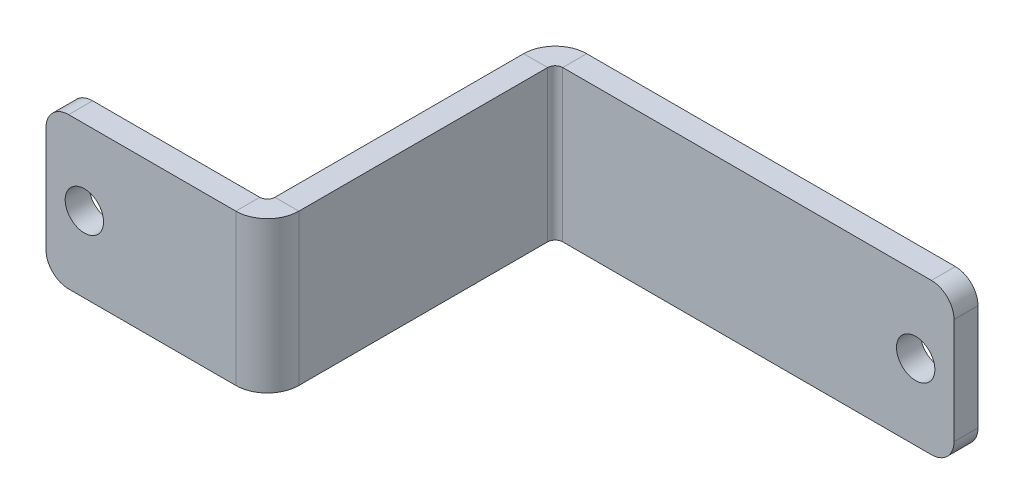
SolidWorks part; units mm, degrees
note: The reader was unsure of these and kept them because the rebuilt part matched: flange length of "Edge-Flange1", "Edge-Flange2".
material "Custom Plastic"
ref_plane "X-Y Datum" through (0, 0, 0) normal (0, 0, 1) x (1, 0, 0)
ref_plane "X-Z Datum" through (0, 0, 0) normal (0, 1, 0) x (1, 0, 0)
ref_plane "Y-Z Datum" through (0, 0, 0) normal (1, 0, 0) x (0, 0, -1)
sketch "Sketch1" plane through (0, 0, -1949.6834) normal (0, 0, 1) x (1, 0, 0)
  line L7 (74.8293, 321.1281) -> (100.9696, 321.1281)
  line L8 (74.8293, 321.1281) -> (74.8293, 301.1281)
  line L9 (74.8293, 301.1281) -> (100.9696, 301.1281)
  line L10 (100.9696, 321.1281) -> (100.9696, 301.1281)
  point P4 (0, 0)
  point P5 (0, 0)
  point P10 (74.8293, 311.1281)
base flange "Base-Flange1" sketch "Sketch1" thickness 3.175 reverse thickness direction yes parameters "D1"=10
edge flange "Edge-Flange1" sketch "Sketch13" flange angle 90 flange length 38.1204 flange position material outside bend radius 1 thickness 3.175 relief rectangular parameters "D6"=10
bend "EdgeBend3" bend radius 1 bend angle 90 parameters "D5"=1
sketch "Sketch13" plane through (100.9696, 0, -1949.6834) normal (-1, 0, 0) x (0, 1, 0)
  line L0 (321.1281, 0) -> (301.1281, 0) construction
  line L1 (321.1281, 0) -> (301.1281, 0)
  line L2 (321.1281, 0) -> (321.1281, 34.9454)
  line L3 (321.1281, 34.9454) -> (301.1281, 34.9454)
  line L4 (301.1281, 34.9454) -> (301.1281, 0)
edge flange "Edge-Flange2" sketch "Sketch15" flange angle 90 flange length 56 flange position material outside bend radius 1 thickness 3.175 relief rectangular parameters "D6"=10
bend "EdgeBend4" bend radius 1 bend angle 90 parameters "D5"=2
sketch "Sketch15" plane through (104.1446, 0, -1984.6288) normal (0, 0, 1) x (0, -1, 0)
  line L0 (-301.1281, 0) -> (-321.1281, 0) construction
  line L1 (-301.1281, 0) -> (-321.1281, 0)
  line L2 (-301.1281, 0) -> (-301.1281, 52.825)
  line L3 (-301.1281, 52.825) -> (-321.1281, 52.825)
  line L4 (-321.1281, 52.825) -> (-321.1281, 0)
fillet "Fillet1" radius 3 4 edges at (74.8293, 301.1281, -1948.0959) (74.8293, 321.1281, -1948.0959) (156.9696, 301.1281, -1986.2163) (156.9696, 321.1281, -1986.2163)
sketch "Sketch18" plane through (0, 0, -1946.5084) normal (0, 0, 1) x (1, 0, 0)
  line L0 (74.8293, 311.1281) -> (79.9093, 311.1281)
  line L1 (74.8293, 318.1281) -> (74.8293, 304.1281) construction
  circle A0 centre (79.9093, 311.1281) radius 2.54
  dimension "D1" = 5.08
extrude "Cut-Extrude2" cut sketch "Sketch18" against normal through all
sketch "Sketch19" plane through (0, 0, -1984.6288) normal (0, 0, 1) x (1, 0, 0)
  line L0 (156.9696, 311.1281) -> (151.8896, 311.1281)
  line L1 (156.9696, 304.1281) -> (156.9696, 318.1281) construction
  circle A0 centre (151.8896, 311.1281) radius 2.54
  dimension "D1" = 5.08
  dimension "D2" = 5.08
extrude "Cut-Extrude3" cut sketch "Sketch19" against normal through all
sketch "Bend-Lines1" [suppressed] plane through (0, 0, 0) normal (0, 1, 0) x (1, 0, 0)
sketch "Bounding-Box1" [suppressed] plane through (0, 0, 0) normal (0, 1, 0) x (1, 0, 0)
sheet metal parameters "Sheet-Metal1" thickness 3.175 parameters "D1"=10
flat pattern "Flat-Pattern1" [suppressed]
sketch "Bend-Lines2" plane through (0, 0, 0) normal (0, 1, 0) x (1, 0, 0)
sketch3d "Bounding-Box2" [suppressed]
  line L0 (-74.8293, 301.1281, 0) -> (-100.9696, 301.1281, 0) construction
  line L1 (-74.8293, 321.1281, 0) -> (-100.9696, 321.1281, 0) construction
  line L2 (-74.8293, 301.1281, 0) -> (-74.8293, 321.1281, 0) construction
  line L3 (-100.9696, 301.1281, 0) -> (-100.9696, 321.1281, 0) construction
sheet metal parameters "Sheet-Metal2" thickness 3.175 parameters "D1"=10
flat pattern "Flat-Pattern1"
sketch "Bend-Lines2" plane through (0, 0, -1947.5) normal (0, 0, -1) x (-1, 0, 0)
  line L2 (-102.0018, 321.1281) -> (-102.0018, 301.1281) construction
  line L3 (-102.0018, 321.1281) -> (-102.0018, 301.1281) construction
sketch3d "Bounding-Box2" [suppressed]
  line L0 (-74.8293, 301.1281, 0) -> (-139.859, 301.1281, 0) construction
  line L1 (-74.8293, 321.1281, 0) -> (-139.859, 321.1281, 0) construction
  line L2 (-74.8293, 301.1281, 0) -> (-74.8293, 321.1281, 0) construction
  line L3 (-139.859, 301.1281, 0) -> (-139.859, 321.1281, 0) construction
bend of the flat pattern "Flatten-<EdgeBend3>1"
sheet metal parameters "Sheet-Metal3" thickness 3.175 parameters "D1"=10
flat pattern "Flat-Pattern1"
sketch "Bend-Lines2" plane through (0, 0, -1947.295) normal (0, 0, -1) x (-1, 0, 0)
  line L4 (-140.8913, 321.1281) -> (-140.8913, 301.1281) construction
  line L5 (-102.0018, 321.1281) -> (-102.0018, 301.1281) construction
  line L6 (-140.8913, 321.1281) -> (-140.8913, 301.1281) construction
  line L7 (-102.0018, 321.1281) -> (-102.0018, 301.1281) construction
sketch3d "Bounding-Box2" [suppressed]
  line L0 (-74.8293, 301.1281, 0) -> (-188.7485, 301.1281, 0) construction
  line L1 (-74.8293, 321.1281, 0) -> (-188.7485, 321.1281, 0) construction
  line L2 (-74.8293, 301.1281, 0) -> (-74.8293, 321.1281, 0) construction
  line L3 (-188.7485, 301.1281, 0) -> (-188.7485, 321.1281, 0) construction
bend of the flat pattern "Flatten-<EdgeBend3>2"
bend of the flat pattern "Flatten-<EdgeBend4>1"
sheet metal parameters "Sheet-Metal5" thickness 3.175 parameters "D1"=10
flat pattern "Flat-Pattern1" [suppressed]
sketch "Bend-Lines2" plane through (0, 0, -1947.295) normal (0, 0, -1) x (-1, 0, 0)
  line L4 (-140.8913, 321.1281) -> (-140.8913, 301.1281) construction
  line L5 (-102.0018, 321.1281) -> (-102.0018, 301.1281) construction
  line L6 (-140.8913, 321.1281) -> (-140.8913, 301.1281) construction
  line L7 (-102.0018, 321.1281) -> (-102.0018, 301.1281) construction
sketch3d "Bounding-Box2" [suppressed]
  line L0 (-74.8293, 301.1281, 0) -> (-188.7485, 301.1281, 0) construction
  line L1 (-74.8293, 321.1281, 0) -> (-188.7485, 321.1281, 0) construction
  line L2 (-74.8293, 301.1281, 0) -> (-74.8293, 321.1281, 0) construction
  line L3 (-188.7485, 301.1281, 0) -> (-188.7485, 321.1281, 0) construction
bend of the flat pattern "Flatten-<EdgeBend3>2"
bend of the flat pattern "Flatten-<EdgeBend4>1"
sketch "Sketch19-1" [suppressed] plane through (37.7789, 0, -1944.12) normal (0, 0, 1) x (1, 0, 0)
  line L0 (150.9696, 311.1281) -> (145.8896, 311.1281)
  circle A0 centre (145.8896, 311.1281) radius 2.54
  dimension "D1" = 5.08
  dimension "D2" = 5.08
sheet metal parameters "Sheet-Metal6" thickness 3.175 parameters "D1"=10
flat pattern "Flat-Pattern1" [suppressed]
sketch "Bend-Lines2" plane through (0, 0, -1949.6834) normal (0, 0, -1) x (-1, 0, 0)
  line L4 (-139.0117, 321.1281) -> (-139.0117, 301.1281) construction
  line L5 (-102.0018, 321.1281) -> (-102.0018, 301.1281) construction
  line L6 (-139.0117, 321.1281) -> (-139.0117, 301.1281) construction
  line L7 (-102.0018, 321.1281) -> (-102.0018, 301.1281) construction
sketch3d "Bounding-Box2" [suppressed]
  line L0 (-74.8293, 301.1281, 0) -> (-192.8689, 301.1281, 0) construction
  line L1 (-74.8293, 321.1281, 0) -> (-192.8689, 321.1281, 0) construction
  line L2 (-74.8293, 301.1281, 0) -> (-74.8293, 321.1281, 0) construction
  line L3 (-192.8689, 301.1281, 0) -> (-192.8689, 321.1281, 0) construction
bend of the flat pattern "Flatten-<EdgeBend3>2"
bend of the flat pattern "Flatten-<EdgeBend4>1"
sketch "Sketch19-1" plane through (35.8993, 0, -1946.5084) normal (0, 0, 1) x (1, 0, 0)
  line L0 (156.9696, 311.1281) -> (151.8896, 311.1281)
  circle A0 centre (151.8896, 311.1281) radius 2.54
  dimension "D1" = 5.08
  dimension "D2" = 5.08
